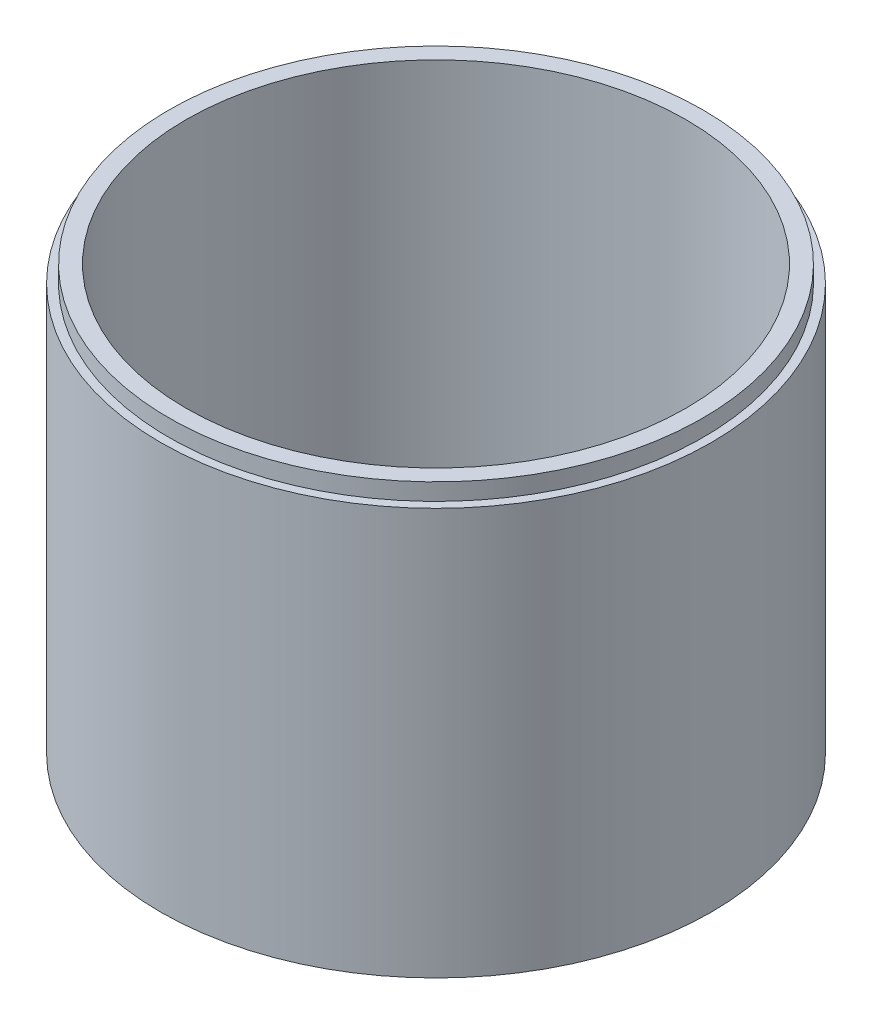
SolidWorks part; units mm, degrees
material "HYPALON"
ref_plane "Front Plane" through (0, 0, 0) normal (0, 0, 1) x (1, 0, 0)
ref_plane "Top Plane" through (0, 0, 0) normal (0, 1, 0) x (1, 0, 0)
ref_plane "Right Plane" through (0, 0, 0) normal (1, 0, 0) x (0, 0, -1)
sketch "Szkic1" plane through (0, 0, 0) normal (0, 0, 1) x (1, 0, 0)
  line L0 (0, 0) -> (-65, 0)
  line L1 (-65, 0) -> (-65, 4)
  line L2 (-63, 4) -> (-59, 4)
  line L3 (-59, 4) -> (-59, 100)
  line L4 (-63, 4) -> (-63, 0)
  line L5 (-59, 100) -> (-63, 100)
  line L7 (-65, 4) -> (-65, 96)
  line L8 (-65, 96) -> (-63, 96)
  line L9 (-63, 96) -> (-63, 100)
  line L13 (0, 0) -> (0, 22.4148)
  dimension "D1" = 65
  dimension "D2" = 4
  dimension "D3" = 6
  dimension "D4" = 100
  dimension "D5" = 2
  dimension "D7" = 2
  dimension "D8" = 4
revolve "Obrót1" add sketch "Szkic1" angle 360 about L13 region at (-62, 50.6667, 0)
